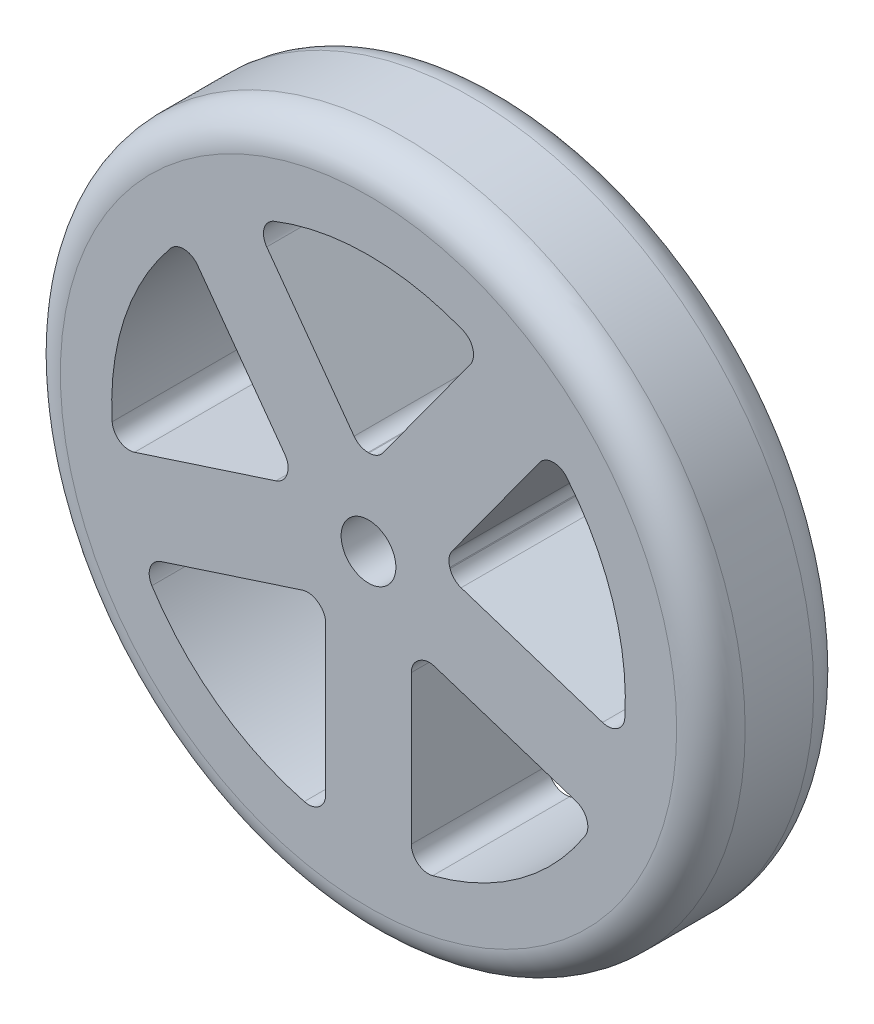
SolidWorks part; units mm, degrees
ref_plane "Plan de face" through (0, 0, 0) normal (0, 0, 1) x (1, 0, 0)
ref_plane "Plan de dessus" through (0, 0, 0) normal (0, 1, 0) x (1, 0, 0)
ref_plane "Plan de droite" through (0, 0, 0) normal (1, 0, 0) x (0, 0, -1)
sketch "Esquisse1" plane through (0, 0, 0) normal (0, 0, 1) x (1, 0, 0)
  circle A0 centre (0, 0) radius 100
  dimension "D1" = 200
extrude "Boss.-Extru.1" add sketch "Esquisse1" along normal blind 40
sketch "Esquisse2" plane through (0, 0, 40) normal (0, 0, 1) x (1, 0, 0)
  line L0 (0, 0) -> (0, 80) construction
  line L1 (2.6132, 24.863) -> (33.3546, 67.1749)
  line L2 (-2.6132, 24.863) -> (-33.3546, 67.1749)
  line L3 (24.4537, 5.1978) -> (74.1943, -10.9639)
  line L4 (22.8386, 10.1684) -> (53.58, 52.4803)
  line L5 (12.5, -21.6506) -> (12.5, -73.951)
  line L6 (16.7283, -18.5786) -> (66.4689, -34.7403)
  line L7 (-16.7283, -18.5786) -> (-66.4689, -34.7403)
  line L8 (-12.5, -21.6506) -> (-12.5, -73.951)
  line L9 (-22.8386, 10.1684) -> (-53.58, 52.4803)
  line L10 (-24.4537, 5.1978) -> (-74.1943, -10.9639)
  arc A0 (-33.3546, 67.1749) -> (33.3546, 67.1749) centre (0, 0) cw
  arc A1 (-2.6132, 24.863) -> (2.6132, 24.863) centre (0, 0) cw
  arc A2 (22.8386, 10.1684) -> (24.4537, 5.1978) centre (0, 0) cw
  arc A3 (53.58, 52.4803) -> (74.1943, -10.9639) centre (0, 0) cw
  arc A4 (16.7283, -18.5786) -> (12.5, -21.6506) centre (0, 0) cw
  arc A5 (66.4689, -34.7403) -> (12.5, -73.951) centre (0, 0) cw
  arc A6 (-12.5, -21.6506) -> (-16.7283, -18.5786) centre (0, 0) cw
  arc A7 (-12.5, -73.951) -> (-66.4689, -34.7403) centre (0, 0) cw
  arc A8 (-24.4537, 5.1978) -> (-22.8386, 10.1684) centre (0, 0) cw
  arc A9 (-74.1943, -10.9639) -> (-53.58, 52.4803) centre (0, 0) cw
  circle A10 centre (0, 0) radius 100 construction
  point P8 (5.3306, 19.2765)
  point P25 (0, 0)
  dimension "D1" = 25
  dimension "D2" = 25
  dimension "D4" = 25
  dimension "D3" = 5
extrude "Enlèv. mat.-Extru.1" cut sketch "Esquisse2" against normal through all both and the other way through all
sketch "Esquisse3" plane through (0, 0, 40) normal (0, 0, 1) x (1, 0, 0)
  circle A0 centre (0, 0) radius 8
  dimension "D1" = 16
extrude "Enlèv. mat.-Extru.2" cut sketch "Esquisse3" against normal through all both and the other way through all
fillet "Congé1" radius 5 20 edges at (-24.4537, 5.1978, 20) (-22.8386, 10.1684, 20) (-2.6132, 24.863, 20) (2.6132, 24.863, 20) (22.8386, 10.1684, 20) (24.4537, 5.1978, 20) (16.7283, -18.5786, 20) (12.5, -21.6506, 20) (-12.5, -21.6506, 20) (-16.7283, -18.5786, 20) (66.4689, -34.7403, 20) (12.5, -73.951, 20) (-66.4689, -34.7403, 20) (-12.5, -73.951, 20) (-74.1943, -10.9639, 20) (-53.58, 52.4803, 20) (-33.3546, 67.1749, 20) (33.3546, 67.1749, 20) (53.58, 52.4803, 20) (74.1943, -10.9639, 20)
fillet "Congé2" radius 10 2 edges at (100, 0, 0) (100, 0, 40)
